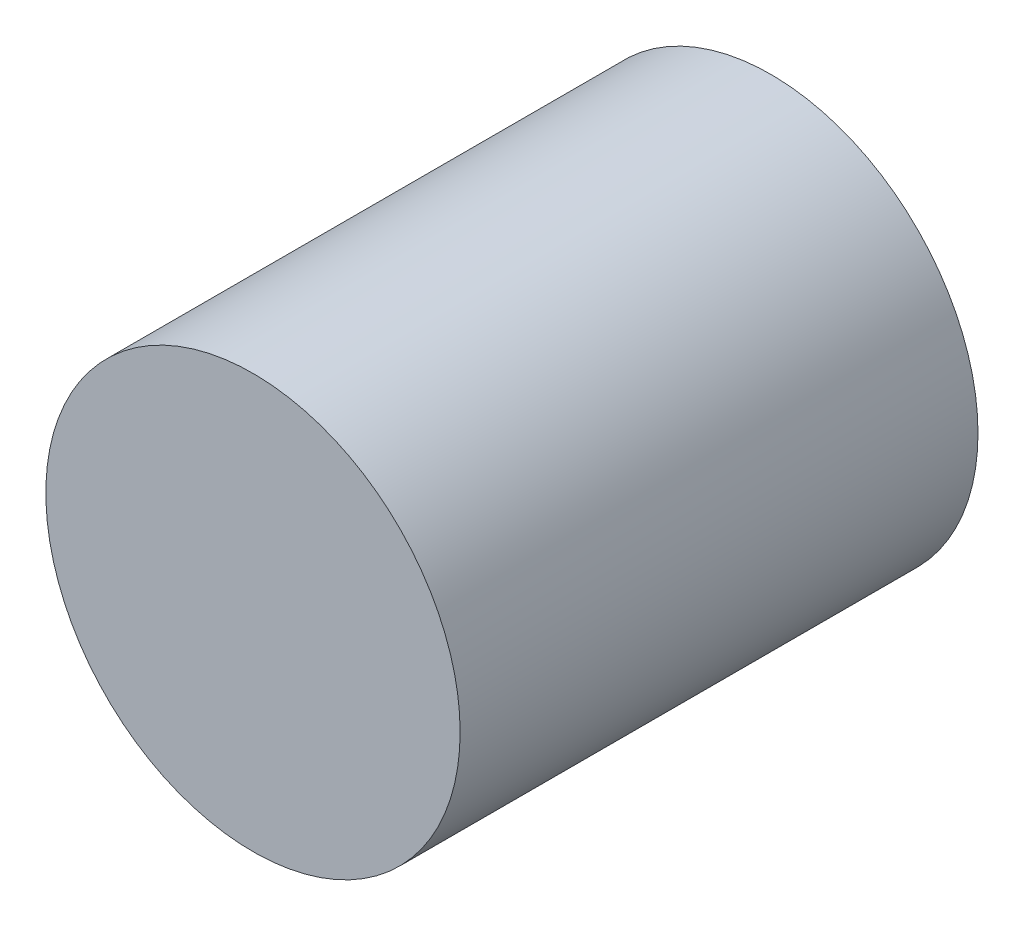
SolidWorks part; units mm, degrees
ref_plane "Front Plane" through (0, 0, 0) normal (0, 0, 1) x (1, 0, 0)
ref_plane "Top Plane" through (0, 0, 0) normal (0, 1, 0) x (1, 0, 0)
ref_plane "Right Plane" through (0, 0, 0) normal (1, 0, 0) x (0, 0, -1)
sketch "Sketch1" plane through (0, 0, 0) normal (0, 0, 1) x (1, 0, 0)
  circle A0 centre (0, 0) radius 12
  dimension "D1" = 24
extrude "Boss-Extrude1" add sketch "Sketch1" along normal blind 30
